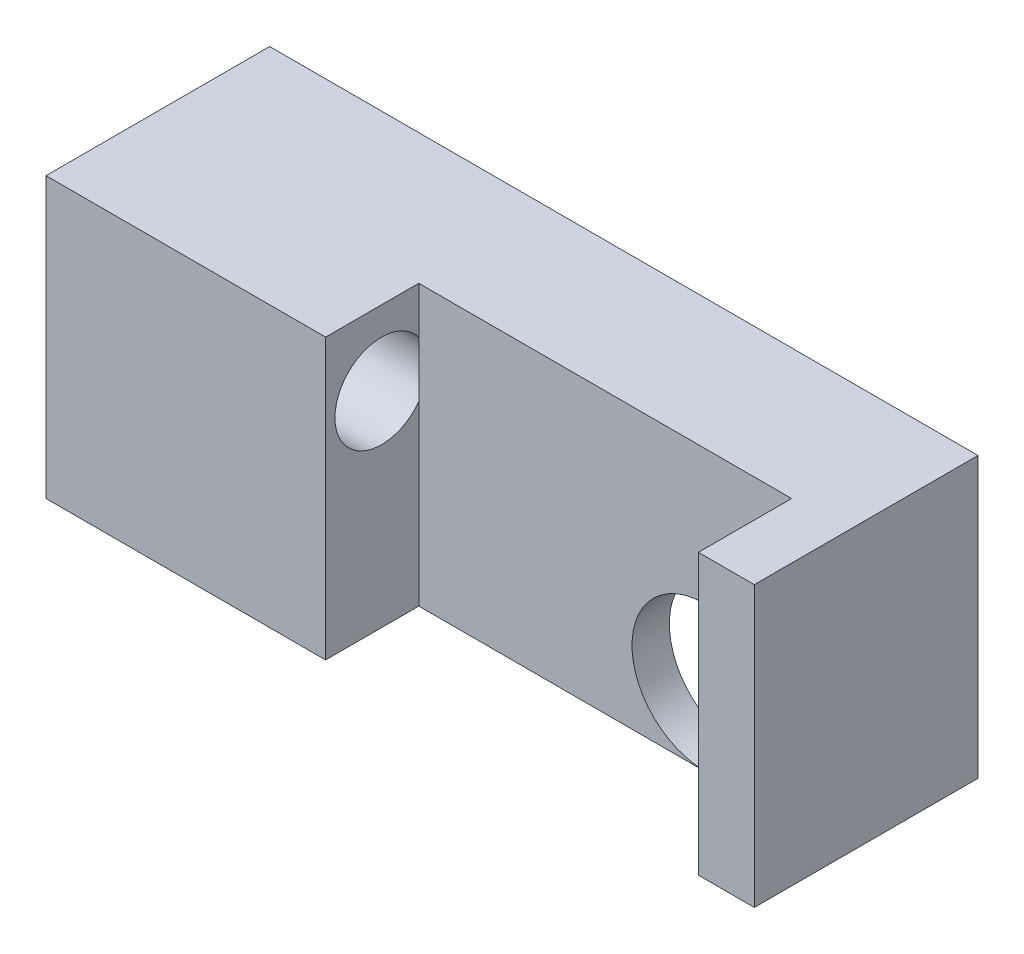
SolidWorks part; units mm, degrees
ref_plane "Ebene vorne" through (0, 0, 0) normal (0, 0, 1) x (1, 0, 0)
ref_plane "Ebene oben" through (0, 0, 0) normal (0, 1, 0) x (1, 0, 0)
ref_plane "Ebene rechts" through (0, 0, 0) normal (1, 0, 0) x (0, 0, -1)
sketch "Sketch1" plane through (0, 0, 0) normal (0, 1, 0) x (1, 0, 0)
  line L1 (0, 0) -> (38, 0)
  line L2 (0, 0) -> (0, 12)
  line L3 (0, 12) -> (38, 12)
  line L4 (38, 0) -> (38, 12)
  dimension "D1" = 38
  dimension "D2" = 12
extrude "Boss-Extrude1" add sketch "Sketch1" along normal blind 15
sketch "Sketch2" plane through (0, 0, 0) normal (-1, 0, 0) x (0, 0, 1)
  line L0 (0, 15) -> (0, 0) construction
  line L1 (-12, 0) -> (0, 0) construction
  circle A0 centre (-3, 11) radius 1.15
  circle A1 centre (-3, 11) radius 2.5
  dimension "D1" = 2.3
  dimension "D4" = 5
  dimension "D2" = 3
  dimension "D3" = 11
extrude "Cut-Extrude1" cut sketch "Sketch2" against normal blind 15 contours A0
sketch "Sketch3" plane through (0, 0, 0) normal (0, 0, 1) x (1, 0, 0)
  line L0 (0, 15) -> (38, 15) construction
  line L1 (15, 15) -> (35, 15)
  line L2 (15, 15) -> (15, 0)
  line L3 (15, 0) -> (35, 0)
  line L4 (35, 15) -> (35, 0)
  line L5 (0, 0) -> (38, 0) construction
  line L6 (0, 15) -> (0, 0) construction
  dimension "D1" = 20
  dimension "D2" = 15
extrude "Cut-Extrude2" cut sketch "Sketch3" against normal blind 5
extrude "Cut-Extrude3" cut sketch "Sketch2<3>" against normal up to surface (15 mm away) from offset 6 contours A1 up to face at (15, 7.5, -2.5) offset against normal yes
sketch "Sketch2<3>" plane through (0, 0, 0) normal (-1, 0, 0) x (0, 0, 1) same geometry as "Sketch2"
sketch "Sketch4" plane through (0, 0, -12) normal (0, 0, -1) x (-1, 0, 0)
  line L0 (-38, 0) -> (0, 0) construction
  line L1 (-33.2426, 0) -> (-9.7575, 0)
  line L2 (-33.2426, 0) -> (-33.2426, 8.6045)
  line L3 (-33.2426, 8.6045) -> (-9.7575, 8.6045)
  line L4 (-9.7575, 0) -> (-9.7575, 8.6045)
extrude "Cut-Extrude4" cut sketch "Sketch4" against normal blind 5
sketch "Sketch5" plane through (0, 0, -5) normal (0, 0, 1) x (1, 0, 0)
  circle A0 centre (30.3251, 3.9042) radius 3.8867
extrude "Cut-Extrude5" cut sketch "Sketch5" against normal up to surface (2 mm away) up to face at (21.5, 4.3022, -7)
